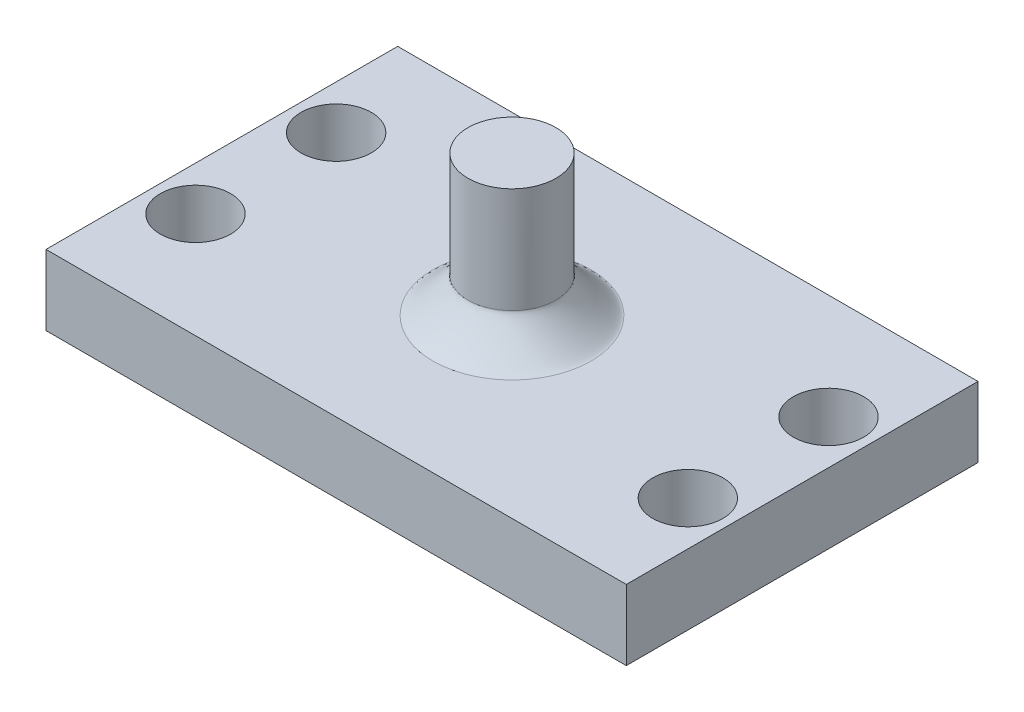
SolidWorks part; units mm, degrees
ref_plane "Front Plane" through (0, 0, 0) normal (0, 0, 1) x (1, 0, 0)
ref_plane "Top Plane" through (0, 0, 0) normal (0, 1, 0) x (1, 0, 0)
ref_plane "Right Plane" through (0, 0, 0) normal (1, 0, 0) x (0, 0, -1)
sketch "Sketch1" plane through (0, 0, 0) normal (0, 1, 0) x (1, 0, 0)
  line L1 (16.5, -10) -> (-16.5, -10)
  line L2 (16.5, -10) -> (16.5, 10)
  line L3 (16.5, 10) -> (-16.5, 10)
  line L4 (-16.5, -10) -> (-16.5, 10)
  line L5 (16.5, -10) -> (-16.5, 10) construction
  line L6 (16.5, 10) -> (-16.5, -10) construction
  point P0 (0, 0)
  dimension "D1" = 33
  dimension "D2" = 20
extrude "Boss-Extrude1" add sketch "Sketch1" along normal mid plane 4
sketch "Sketch2" plane through (0, 2, 0) normal (0, 1, 0) x (1, 0, 0)
  line L0 (-14, 4) -> (-14, -4) construction
  line L1 (-14, 0) -> (0, 0) construction
  line L2 (0, 0) -> (0, -10) construction
  line L3 (-16.5, -10) -> (16.5, -10) construction
  circle A0 centre (-14, 4) radius 2
  circle A1 centre (-14, -4) radius 2
  circle A4 centre (14, -4) radius 2
  circle A5 centre (14, 4) radius 2
  dimension "D1" = 4
  dimension "D2" = 14
  dimension "D3" = 8
extrude "Cut-Extrude1" cut sketch "Sketch2" against normal through all
sketch "Sketch3" plane through (0, 2, 0) normal (0, 1, 0) x (1, 0, 0)
  circle A0 centre (0, 0) radius 2.5
  dimension "D1" = 5
extrude "Boss-Extrude2" add sketch "Sketch3" along normal blind 8
fillet "Fillet1" radius 2 1 edges at (0, 2, 2.5) conic radius 10
